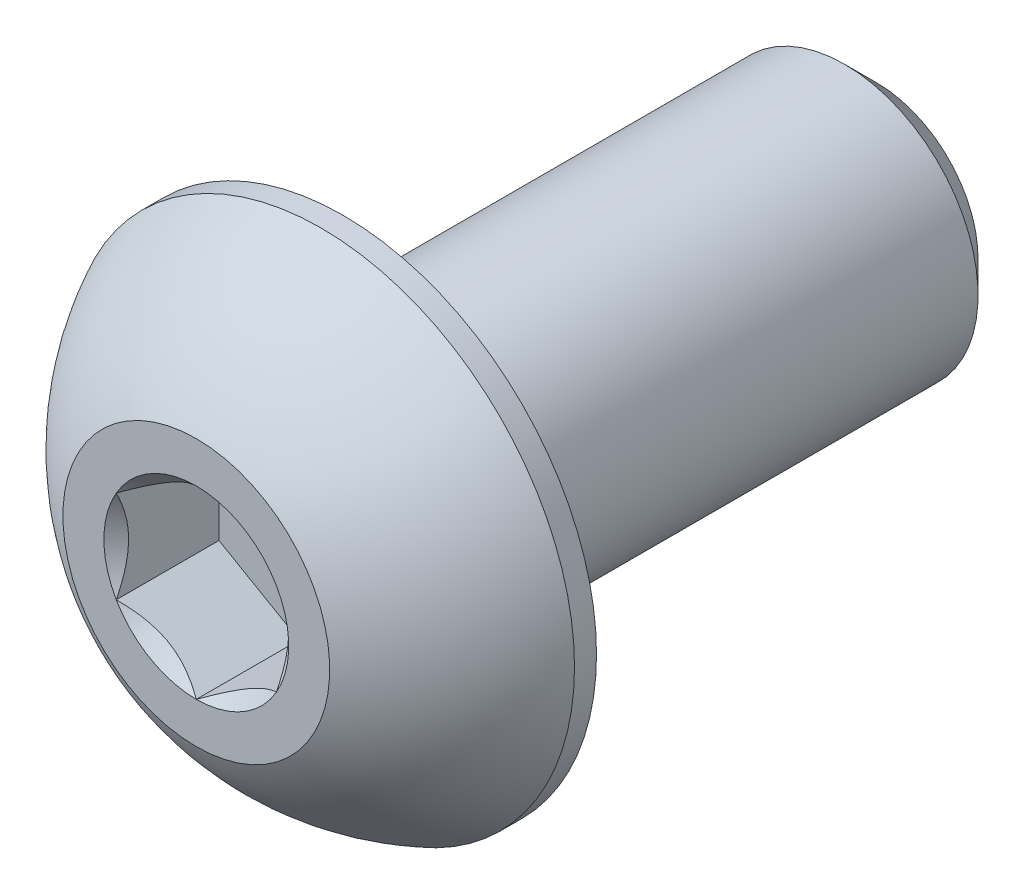
SolidWorks part; units mm, degrees
ref_plane "Front" through (0, 0, 0) normal (0, 0, 1) x (1, 0, 0)
ref_plane "Top" through (0, 0, 0) normal (0, 1, 0) x (1, 0, 0)
ref_plane "Right" through (0, 0, 0) normal (1, 0, 0) x (0, 0, -1)
sketch "Sketch1" plane through (0, 0, 0) normal (1, 0, 0) x (0, 0, -1)
  line L2 (2.75, 2.5) -> (12.75, 2.5)
  line L3 (12.75, 2.5) -> (12.75, 0)
  line L4 (12.75, 0) -> (2.75, 0)
  line L6 (2.3375, 4.75) -> (2.75, 4.75) construction
  line L7 (12.75, 2.5) -> (12.75, -2.5) construction
  line L8 (0, 0) -> (2.75, 0) construction
  line L9 (2.75, 4.75) -> (2.75, -4.75) construction
  line L11 (2.75, 2.5) -> (2.75, 0)
  line L13 (0, 1.5) -> (0, -1.5) construction
  line L14 (0, 1.5) -> (0, 2.5) construction
  arc A3 (0, 2.5) -> (2.3375, 4.75) centre (4.6581, 0) cw construction
  dimension "D1" = 0.4125
revolve "Revolve1" add sketch "Sketch1" angle 360 mid plane about L4
sketch "Sketch3" plane through (0, 0, -12.75) normal (0, 0, -1) x (-1, 0, 0)
  circle A0 centre (0, 0) radius 2.5
curve "Helix/Spiral1" pitch 0.8 height 10.8 turns 13.5
chamfer "Chamfer1" distance 0.6 angle 45 1 edges at (0, 2.5, -12.75)
sketch "Sketch7" plane through (0, 0, 0) normal (1, 0, 0) x (0, 0, -1)
  line L6 (2.3375, 4.75) -> (2.75, 4.75) construction
  line L8 (0, 0) -> (2.75, 0) construction
  line L11 (2.75, 4.75) -> (2.75, -4.75) construction
  line L12 (2.3375, 4.75) -> (2.75, 4.75)
  line L13 (0, 0) -> (2.75, 0)
  line L14 (0, 1.5) -> (0, -1.5) construction
  line L15 (2.75, 4.75) -> (2.75, 0)
  line L16 (0, 2.5) -> (0, 0)
  arc A2 (2.3375, 4.75) -> (0, 2.5) centre (4.6581, 0) ccw construction
  arc A3 (2.3375, 4.75) -> (0, 2.5) centre (4.6581, 0) ccw
revolve "Revolve2" add sketch "Sketch7" angle 360 mid plane about L13
sketch "Sketch5" plane through (0, 0, 0) normal (0, 0, 1) x (1, 0, 0)
  line L1 (1.5, -0.866) -> (1.5, 0.866)
  line L2 (1.5, 0.866) -> (0, 1.7321)
  line L3 (0, 1.7321) -> (-1.5, 0.866)
  line L4 (-1.5, 0.866) -> (-1.5, -0.866)
  line L5 (-1.5, -0.866) -> (0, -1.7321)
  line L6 (0, -1.7321) -> (1.5, -0.866)
  circle A0 centre (0, 0) radius 1.5 construction
extrude "Cut-Extrude2" cut sketch "Sketch5" against normal blind 1.925
sketch "Sketch6" plane through (0, 0, 0) normal (0, 0, 1) x (1, 0, 0)
  circle A0 centre (0, 0) radius 1.7321
extrude "Cut-Extrude3" cut sketch "Sketch6" against normal blind 1.925 draft 45
sketch "Sketch2" plane through (0, 0, 0) normal (1, 0, 0) x (0, 0, -1)
  line L0 (12.15, 2.5) -> (12.85, 2.5)
  line L1 (12.85, 2.5) -> (12.55, 1.9804)
  line L2 (12.55, 1.9804) -> (12.45, 1.9804)
  line L3 (12.45, 1.9804) -> (12.15, 2.5)
  line L4 (12.3, 2.2402) -> (12.7, 2.2402) construction
  dimension "D1" = 60
  dimension "D2" = 0.1
  dimension "D3" = 0.4
sweep "Cut-Sweep1" [suppressed] cut profiles "Sketch2" path "Helix/Spiral1"
sketch "Sketch10" plane through (0, 0, 0) normal (1, 0, 0) x (0, 0, -1)
  line L0 (12.75, 2.5) -> (12.75, -2.5) construction
  point P0 (11.55, -2.5)
  dimension "D1" = 1.2
ref_axis "Center Axis 1" through (0, 0, -8.1113) along (0, 0, 1)
ref_plane "Contact Plane 1" through (0, 0, -2.75) normal (0, 0, -1) x (-1, 0, 0)
ref_plane "Contact Plane 2" through (0, 0, 0) normal (0, 0, 1) x (1, 0, 0)
equation "\"D3@Helix/Spiral1\" = \"Lg@Sketch1\" + \"D4@Helix/Spiral1\""
equation "\"D2@Sketch2\" = \"D4@Helix/Spiral1\" * .125"
equation "\"D3@Sketch2\" = \"D4@Helix/Spiral1\" * .5"
equation "\"D1@Chamfer1\" = \"D4@Helix/Spiral1\" * .75"
equation "\"D1@Cut-Extrude2\" = \"Head Ht@Sketch1\" * .7"
equation "\"D1@Sketch1\" = \"Head Ht@Sketch1\" * .15"
equation "\"D1@Sketch10\" = \"D4@Helix/Spiral1\" * 1.5"
equation "\"D1@Cut-Extrude3\" = \"D1@Cut-Extrude2\""
